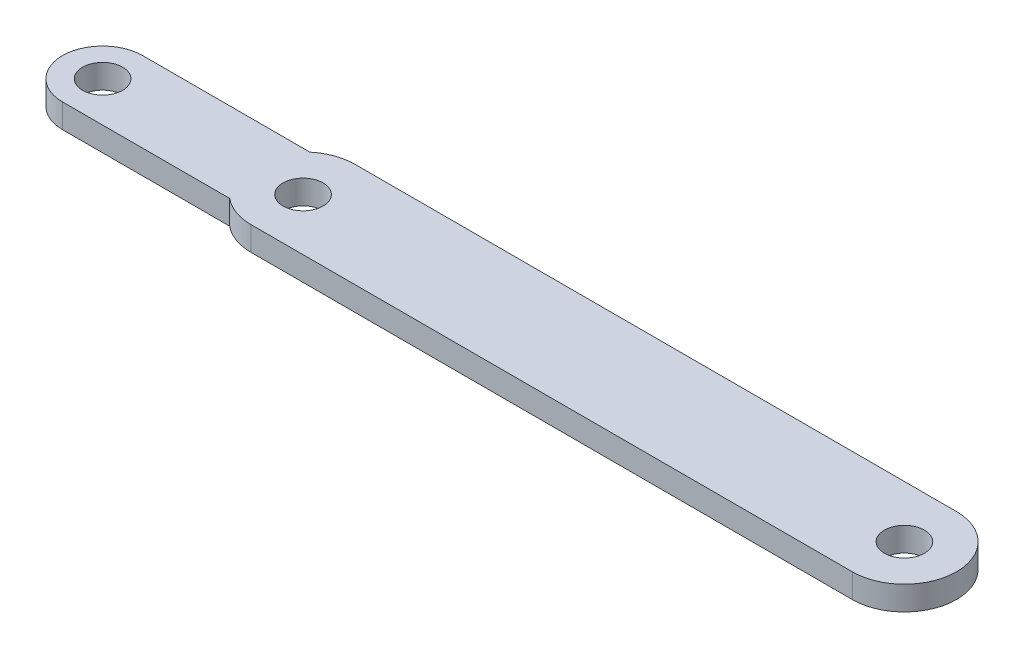
SolidWorks part; units mm, degrees
ref_plane "Front Plane" through (0, 0, 0) normal (0, 0, 1) x (1, 0, 0)
ref_plane "Top Plane" through (0, 0, 0) normal (0, 1, 0) x (1, 0, 0)
ref_plane "Right Plane" through (0, 0, 0) normal (1, 0, 0) x (0, 0, -1)
sketch "Sketch2" plane through (0, 0, 0) normal (0, 1, 0) x (1, 0, 0)
  line L1 (12.5936, 198.8185) -> (87.5936, 198.8185)
  line L3 (12.5936, 185.8185) -> (87.5936, 185.8185)
  line L4 (12.5936, 187.3185) -> (-12.4064, 187.3185)
  line L6 (12.5936, 197.3185) -> (-12.4064, 197.3185)
  arc A0 (87.5936, 198.8185) -> (87.5936, 185.8185) centre (87.5936, 192.3185) cw
  circle A1 centre (87.5936, 192.3185) radius 2.5
  arc A2 (12.5936, 198.8185) -> (12.5936, 185.8185) centre (12.5936, 192.3185) ccw
  arc A3 (-12.4064, 197.3185) -> (-12.4064, 187.3185) centre (-12.4064, 192.3185) ccw
  circle A4 centre (-12.4064, 192.3185) radius 2.5
  circle A5 centre (12.5936, 192.3185) radius 2.5
  dimension "D3" = 5
  dimension "D7" = 5
  dimension "D8" = 5
  dimension "D1" = 75
  dimension "D2" = 13
  dimension "D4" = 1.5
  dimension "D5" = 1.5
  dimension "D6" = 25
extrude "Boss-Extrude1" add sketch "Sketch2" along normal blind 3 contours L6 A3 L4 A2 A4 | L1 A2 L3 A0 A5 A1 region at (50.0936, 0, -192.3185) region at (-4.0722, 0, -192.3185)
